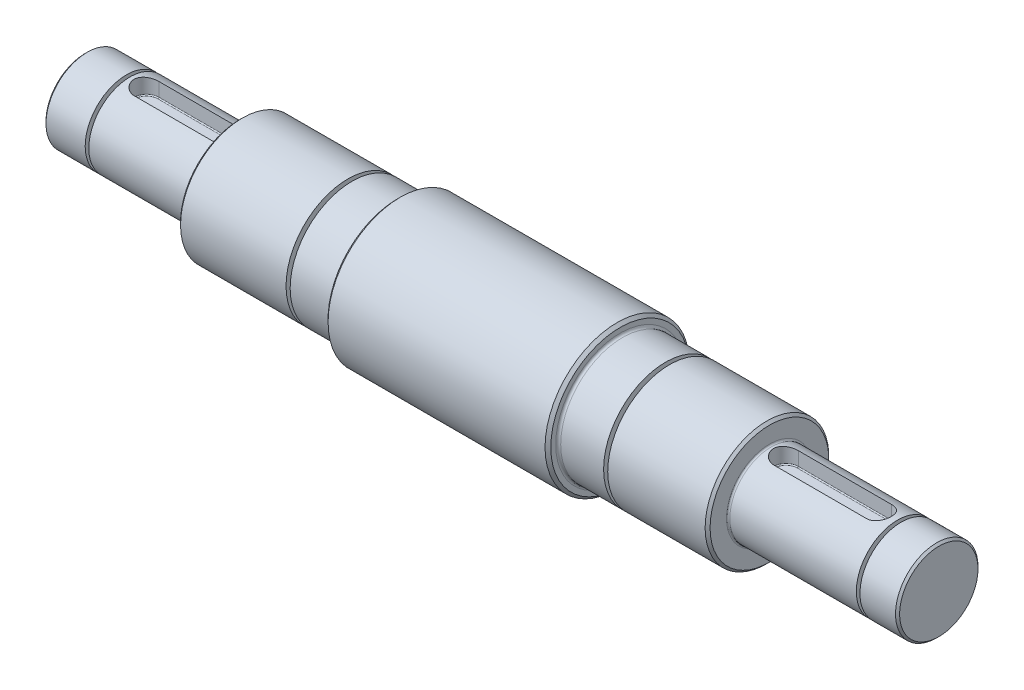
SolidWorks part; units mm, degrees
ref_plane "Front Plane" through (0, 0, 0) normal (0, 0, 1) x (1, 0, 0)
ref_plane "Top Plane" through (0, 0, 0) normal (0, 1, 0) x (1, 0, 0)
ref_plane "Right Plane" through (0, 0, 0) normal (1, 0, 0) x (0, 0, -1)
sketch "Sketch2" plane through (0, 0, 0) normal (0, 0, 1) x (1, 0, 0)
  line L0 (-181.6075, 0) -> (181.6075, 0) construction
  line L3 (-137.3075, 20) -> (-137.3075, 30)
  line L5 (-212.3575, 20) -> (-212.3575, 0)
  line L6 (-212.3575, 0) -> (-181.6075, 0)
  line L7 (-137.3075, 30) -> (-84.9575, 30)
  line L8 (-60.9575, 30) -> (-60.9575, 35)
  line L9 (-60.9575, 35) -> (47.0425, 35)
  line L10 (47.0425, 35) -> (47.0425, 30)
  line L11 (47.0425, 30) -> (119.4775, 30)
  line L12 (119.4775, 30) -> (119.4775, 20)
  line L13 (119.4775, 20) -> (181.6075, 20)
  line L14 (181.6075, 20) -> (181.6075, 0)
  line L15 (181.6075, 0) -> (-181.6075, 0)
  line L25 (-192.3575, 20) -> (-212.3575, 20)
  line L26 (-190.6075, 20) -> (-137.3075, 20)
  line L27 (-190.6075, 15.6) -> (-190.6075, 20) construction
  line L29 (-83.9575, 30) -> (-83.9575, 0) construction
  line L30 (-82.9575, 30) -> (-82.9575, 24.2)
  line L31 (-84.9575, 30) -> (-84.9575, 24.2)
  line L32 (-84.9575, 24.2) -> (-82.9575, 24.2)
  line L33 (-82.9575, 30) -> (-60.9575, 30)
  line L34 (-84.9575, 30) -> (-82.9575, 30) construction
  line L36 (-192.3575, 20) -> (-192.3575, 15.6)
  line L37 (-192.3575, 15.6) -> (-190.6075, 15.6)
  line L38 (-190.6075, 15.6) -> (-190.6075, 20)
  point P4 (0, 0)
  point P19 (-190.6075, 20)
  dimension "D13" = 53.3
  dimension "D1" = 363.215
  dimension "D2" = 10
  dimension "D3" = 4.4
  dimension "D4" = 20
  dimension "D5" = 1.75
  dimension "D6" = 20
  dimension "D7" = 62.13
  dimension "D8" = 72.435
  dimension "D9" = 30
  dimension "D10" = 35
  dimension "D11" = 108
  dimension "D12" = 76.35
  dimension "D14" = 20
  dimension "D15" = 23
  dimension "D16" = 1
  dimension "D17" = 1
  dimension "D18" = 5.8
  dimension "D19" = 4.4
revolve "Revolve1" add sketch "Sketch2" angle 360 about L0
ref_plane "Plane1" through (-6.9575, 0, 0) normal (1, 0, 0) x (0, 0, -1)
mirror "Mirror1" about plane through (-6.9575, 0, 0) normal (1, 0, 0) of face at (-82.9575, 0, 24.2) of face at (-84.9575, 0, 30) of face at (-84.9575, 0, 24.2)
sketch "Sketch4" plane through (181.6075, 0, 0) normal (1, 0, 0) x (0, 0, -1)
  circle A1 centre (0, 0) radius 20
  circle A2 centre (0, 0) radius 20
  dimension "D1" = 0
extrude "Boss-Extrude1" add sketch "Sketch4" along normal blind 20 separate body
sketch "Sketch5" plane through (0, 0, 0) normal (0, 0, 1) x (1, 0, 0)
  line L0 (181.6075, 20) -> (181.6075, 15.6)
  line L1 (181.6075, 20) -> (181.6075, -20) construction
  line L2 (181.6075, 15.6) -> (183.3575, 15.6)
  line L3 (183.3575, 15.6) -> (183.3575, 20)
  line L4 (201.6075, 20) -> (181.6075, 20) construction
  line L5 (181.6075, 20) -> (183.3575, 20)
  line L6 (201.6075, 0) -> (0, 0) construction
  line L7 (201.6075, -20) -> (201.6075, 20) construction
  dimension "D1" = 4.4
  dimension "D2" = 1.75
revolve "Cut-Revolve1" cut sketch "Sketch5" angle 360 about L6
ref_plane "Plane2" through (-145.3075, 0, 0) normal (-1, 0, 0) x (0, 0, 1)
sketch "Sketch6" plane through (-145.3075, 0, 0) normal (-1, 0, 0) x (0, 0, 1)
  line L0 (0, 20) -> (0, 12) construction
  line L1 (-6, 12) -> (6, 12)
  line L2 (6, 12) -> (6, 19.0788)
  line L3 (-6, 12) -> (-6, 19.0788)
  circle A0 centre (0, 0) radius 20 construction
  arc A1 (6, 19.0788) -> (-6, 19.0788) centre (0, 0) ccw
  point P9 (0, 12)
  dimension "D1" = 12
  dimension "D2" = 8
extrude "Cut-Extrude1" cut sketch "Sketch6" along normal blind 37.3
fillet "Fillet1" radius 0.8 1 edges at (-137.3075, 0, 20)
chamfer "Chamfer1" distance 1.2 angle 45 1 edges at (-137.3075, 0, 30)
fillet "Fillet2" radius 1.2 1 edges at (-60.9575, 0, 30)
chamfer "Chamfer2" distance 1.4 angle 45 1 edges at (-60.9575, 0, 35)
chamfer "Chamfer3" distance 1.4 angle 45 1 edges at (47.0425, 0, 35)
fillet "Fillet3" radius 1.2 1 edges at (47.0425, 0, 30)
chamfer "Chamfer4" distance 1.2 angle 45 1 edges at (119.4775, 0, 30)
fillet "Fillet4" radius 0.8 1 edges at (119.4775, 0, 20)
ref_plane "Plane3" through (127.4775, 0, 0) normal (1, 0, 0) x (0, 0, -1)
sketch "Sketch7" plane through (127.4775, 0, 0) normal (1, 0, 0) x (0, 0, -1)
  line L0 (0, 20) -> (0, 12) construction
  line L1 (-6, 12) -> (6, 12)
  line L2 (6, 12) -> (6, 19.0788)
  line L3 (-6, 12) -> (-6, 19.0788)
  circle A0 centre (0, 0) radius 20 construction
  arc A1 (6, 19.0788) -> (-6, 19.0788) centre (0, 0) ccw
  point P9 (0, 12)
  dimension "D1" = 12
  dimension "D2" = 8
extrude "Cut-Extrude2" cut sketch "Sketch7" along normal blind 45.13
ref_plane "Plane4" through (0, 20, 0) normal (0, 1, 0) x (1, 0, 0)
sketch "Sketch8" plane through (0, 20, 0) normal (0, 1, 0) x (1, 0, 0)
  line L0 (-145.3075, 6) -> (-145.3075, -6) construction
  line L1 (-182.6075, -6) -> (-182.6075, 6) construction
  line L2 (-145.3075, 6) -> (-145.3075, -6)
  line L3 (-182.6075, -6) -> (-182.6075, 6)
  arc A0 (-145.3075, -6) -> (-145.3075, 6) centre (-145.3075, 0) ccw
  arc A1 (-182.6075, 6) -> (-182.6075, -6) centre (-182.6075, 0) ccw
extrude "Cut-Extrude3" cut sketch "Sketch8" against normal up to surface (8 mm away) up to face at (-163.9575, 12, 0)
fillet "Fillet5" radius 0.5 4 edges at (-188.6075, 12, 0) (-163.9575, 12, 6) (-139.3075, 12, 0) (-163.9575, 12, -6)
ref_plane "Plane5" through (0, 20, 0) normal (0, 1, 0) x (1, 0, 0)
sketch "Sketch9" plane through (0, 20, 0) normal (0, 1, 0) x (1, 0, 0)
  line L0 (127.4775, -6) -> (127.4775, 6) construction
  line L1 (172.6075, 6) -> (172.6075, -6) construction
  line L2 (127.4775, 6) -> (127.4775, -6)
  line L3 (172.6075, 6) -> (172.6075, -6)
  arc A0 (127.4775, 6) -> (127.4775, -6) centre (127.4775, 0) ccw
  arc A1 (172.6075, -6) -> (172.6075, 6) centre (172.6075, 0) ccw
extrude "Cut-Extrude4" cut sketch "Sketch9" against normal up to surface (8 mm away) up to face at (150.0425, 12, 0)
fillet "Fillet6" radius 0.4 2 edges at (71.0425, 0, 24.2) (69.0425, 0, 24.2)
fillet "Fillet10" radius 0.4 1 edges at (183.3575, 0, -15.6)
fillet "Fillet12" radius 0.4 2 edges at (-84.9575, 0, 24.2) (-82.9575, 0, 24.2)
fillet "Fillet13" radius 0.4 2 edges at (-192.3575, 0, 15.6) (-190.6075, 0, 15.6)
sketch "Sketch11" plane through (0, 0, 0) normal (0, 0, 1) x (1, 0, 0)
  line L1 (201.6075, 0) -> (183.3575, 0) construction
  line L2 (201.6075, -20) -> (201.6075, 20) construction
  line L3 (181.6075, 16) -> (181.6075, 15.6)
  line L4 (181.6075, -20) -> (181.6075, 20) construction
  line L5 (181.6075, 15.6) -> (181.6075, -15.6) construction
  line L6 (181.6075, 15.6) -> (182.0075, 15.6)
  line L7 (183.3575, 16) -> (183.3575, -16) construction
  arc A0 (182.0075, 15.6) -> (181.6075, 16) centre (182.0075, 16) cw
  dimension "D1" = 0.4
revolve "Revolve3" add sketch "Sketch11" angle 360 about L1
fillet "Fillet14" radius 0.5 4 edges at (178.6075, 12, 0) (150.0425, 12, 6) (121.4775, 12, 0) (150.0425, 12, -6)
chamfer "Chamfer5" distance 1 angle 45 1 edges at (201.6075, 0, -20)
chamfer "Chamfer6" distance 1 angle 45 1 edges at (-212.3575, 0, 20)
